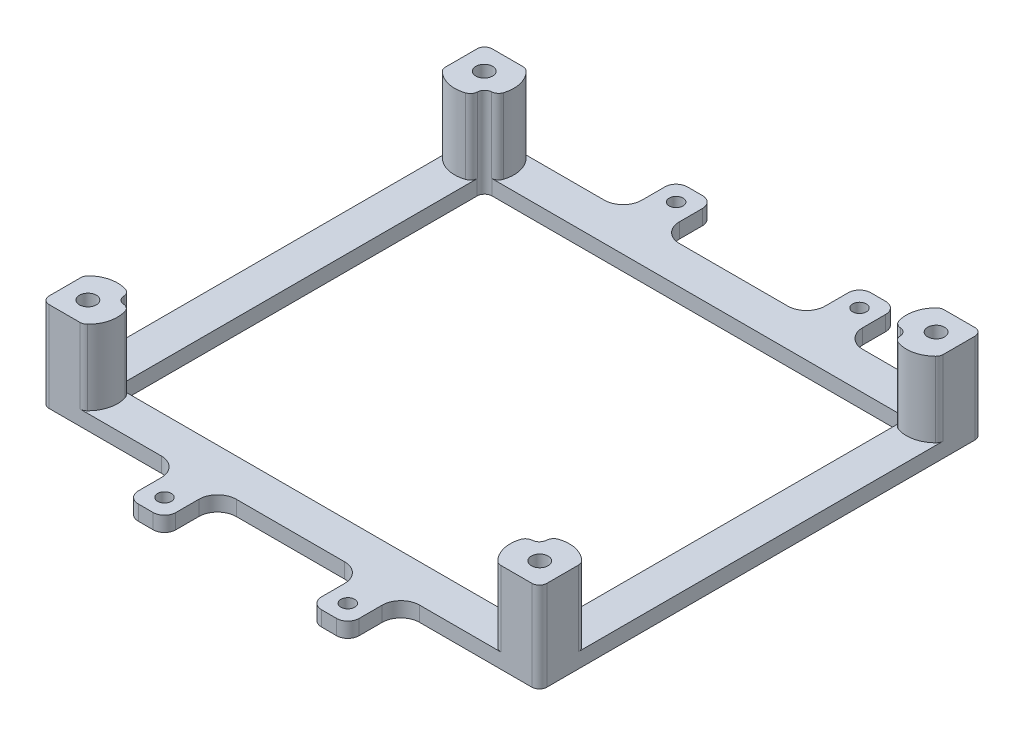
SolidWorks part; units mm, degrees
ref_plane "Front Plane" through (0, 0, 0) normal (0, 0, 1) x (1, 0, 0)
ref_plane "Top Plane" through (0, 0, 0) normal (0, 1, 0) x (1, 0, 0)
ref_plane "Right Plane" through (0, 0, 0) normal (1, 0, 0) x (0, 0, -1)
sketch "Sketch1" plane through (0, 0, 0) normal (0, 1, 0) x (1, 0, 0)
  line L0 (-60.25, 52.85) -> (60.25, -52.85) construction
  line L5 (-60.25, -52.85) -> (60.25, 52.85) construction
  line L6 (-24.4475, -68.2244) -> (24.4475, -68.2244) construction
  line L7 (-66.375, -59.075) -> (66.375, -59.075)
  line L8 (-66.375, -59.075) -> (-66.375, 59.075)
  line L9 (-66.375, 59.075) -> (66.375, 59.075)
  line L10 (66.375, -59.075) -> (66.375, 59.075)
  line L11 (-66.375, -59.075) -> (66.375, 59.075) construction
  line L12 (-66.375, 59.075) -> (66.375, -59.075) construction
  line L13 (-56.375, -49.075) -> (56.375, -49.075)
  line L14 (-56.375, -49.075) -> (-56.375, 49.075)
  line L15 (-56.375, 49.075) -> (56.375, 49.075)
  line L16 (56.375, -49.075) -> (56.375, 49.075)
  line L17 (-56.375, -49.075) -> (56.375, 49.075) construction
  line L18 (-56.375, 49.075) -> (56.375, -49.075) construction
  line L19 (-24.4475, 68.2244) -> (24.4475, 68.2244) construction
  line L20 (-24.4475, 68.2244) -> (-24.4475, -68.2244) construction
  line L21 (0, -55) -> (0, 55) construction
  line L38 (-29.4475, 59.075) -> (-19.4475, 59.075)
  line L39 (-29.4475, 59.075) -> (-29.4475, 73.2244)
  line L40 (-29.4475, 73.2244) -> (-19.4475, 73.2244)
  line L41 (-19.4475, 59.075) -> (-19.4475, 73.2244)
  line L42 (29.4475, 73.2244) -> (19.4475, 73.2244)
  line L43 (19.4475, 59.075) -> (19.4475, 73.2244)
  line L44 (29.4475, 59.075) -> (19.4475, 59.075)
  line L45 (29.4475, 59.075) -> (29.4475, 73.2244)
  line L46 (-55, 0) -> (55, 0) construction
  line L47 (29.4475, -59.075) -> (29.4475, -73.2244)
  line L48 (29.4475, -59.075) -> (19.4475, -59.075)
  line L49 (19.4475, -59.075) -> (19.4475, -73.2244)
  line L50 (29.4475, -73.2244) -> (19.4475, -73.2244)
  line L51 (-29.4475, -73.2244) -> (-19.4475, -73.2244)
  line L52 (-19.4475, -59.075) -> (-19.4475, -73.2244)
  line L53 (-29.4475, -59.075) -> (-19.4475, -59.075)
  line L54 (-29.4475, -59.075) -> (-29.4475, -73.2244)
  circle A0 centre (-60.25, 52.85) radius 2.25
  circle A1 centre (60.25, 52.85) radius 2.25
  circle A2 centre (-60.25, -52.85) radius 2.25
  circle A3 centre (60.25, -52.85) radius 2.25
  circle A4 centre (-24.4475, -68.2244) radius 1.8415
  circle A5 centre (24.4475, -68.2244) radius 1.8415
  circle A6 centre (-24.4475, 68.2244) radius 1.8415
  circle A7 centre (24.4475, 68.2244) radius 1.8415
  arc A8 (-34.4475, 59.075) -> (-29.4475, 64.075) centre (-34.4475, 64.075) ccw
  arc A9 (-14.4475, 59.075) -> (-19.4475, 64.075) centre (-14.4475, 64.075) cw
  arc A10 (34.4475, 59.075) -> (29.4475, 64.075) centre (34.4475, 64.075) cw
  arc A11 (14.4475, 59.075) -> (19.4475, 64.075) centre (14.4475, 64.075) ccw
  arc A12 (34.4475, -59.075) -> (29.4475, -64.075) centre (34.4475, -64.075) ccw
  arc A13 (14.4475, -59.075) -> (19.4475, -64.075) centre (14.4475, -64.075) cw
  arc A14 (-34.4475, -59.075) -> (-29.4475, -64.075) centre (-34.4475, -64.075) cw
  arc A15 (-14.4475, -59.075) -> (-19.4475, -64.075) centre (-14.4475, -64.075) ccw
  point P0 (0, 0)
  point P1 (0, 0)
  point P2 (0, 0)
  point P16 (0, 0)
  point P23 (0, -68.2244)
  point P28 (0, 68.2244)
  point P31 (-24.4475, 0)
  point P76 (0, 59.075)
  point P77 (-66.375, 0)
  dimension "D2" = 4.5
  dimension "D3" = 4.5
  dimension "D4" = 4.5
  dimension "D5" = 4.5
  dimension "D6" = 118.15
  dimension "D11" = 3.683
  dimension "D12" = 3.683
  dimension "D14" = 3.683
  dimension "D15" = 3.683
  dimension "D21" = 10
  dimension "D7" = 132.75
  dimension "D8" = 120.5
  dimension "D9" = 10
  dimension "D10" = 10
  dimension "D13" = 48.895
  dimension "D16" = 48.895
  dimension "D17" = 136.4488
  dimension "D18" = 5
  dimension "D19" = 5
  dimension "D20" = 5
  dimension "D22" = 105.7
extrude "Boss-Extrude3" add sketch "Sketch1" along normal blind 4 contours L9 L41 L40 L39 A6 | L9 L45 L42 L43 A7 | L7 L10 L9 L8 A3 A2 A1 A0 L16 L13 L14 L15 | L7 L54 L51 L52 A4 | L50 L47 L7 L49 A5 | A11 L9 L43 | L9 A10 L45 | A8 L9 L39 | L9 A9 L41 | A15 L7 L52 | L7 A14 L54 | L7 A13 L49 | A12 L7 L47 region at (-64.5979, 0, 0) region at (-30.5643, 0, 60.1918) region at (-24.4475, 0, 65.9808) region at (-30.5643, 0, -60.1918) region at (-18.3307, 0, 60.1918) region at (-24.4475, 0, -65.9808) region at (-18.3307, 0, -60.1918) region at (18.3307, 0, 60.1918) region at (24.4475, 0, 65.9808) region at (18.3307, 0, -60.1918) region at (30.5643, 0, 60.1918) region at (24.4475, 0, -65.9808) region at (30.5643, 0, -60.1918)
fillet "Fillet1" radius 2 8 edges at (56.375, 2, 49.075) (-56.375, 2, 49.075) (56.375, 2, -49.075) (66.375, 2, -59.075) (66.375, 2, 59.075) (-56.375, 2, -49.075) (-66.375, 2, -59.075) (-66.375, 2, 59.075)
fillet "Fillet2" radius 3 8 edges at (-29.4475, 2, -73.2244) (19.4475, 2, -73.2244) (29.4475, 2, -73.2244) (-19.4475, 2, -73.2244) (-29.4475, 2, 73.2244) (-19.4475, 2, 73.2244) (29.4475, 2, 73.2244) (19.4475, 2, 73.2244)
sketch "Sketch3" plane through (0, 4, 0) normal (0, 1, 0) x (1, 0, 0)
  line L0 (-66.375, 47.8504) -> (-66.375, 57.075)
  line L1 (-66.375, -57.075) -> (-66.375, 57.075) construction
  line L2 (-55.3755, 59.075) -> (-64.375, 59.075)
  line L3 (-64.375, 59.075) -> (-34.4475, 59.075) construction
  line L4 (-53.303, 49.075) -> (-54.375, 49.075)
  line L5 (-56.375, 47.075) -> (-56.375, 45.9583)
  line L6 (-56.375, -47.075) -> (-56.375, 47.075) construction
  line L7 (0, -2.2) -> (0, 2.2) construction
  line L8 (56.375, 47.075) -> (56.375, 45.9583)
  line L9 (53.303, 49.075) -> (54.375, 49.075)
  line L10 (55.3755, 59.075) -> (64.375, 59.075)
  line L11 (66.375, 47.8504) -> (66.375, 57.075)
  line L12 (-2.2, 0) -> (2.2, 0) construction
  line L13 (66.375, -47.8504) -> (66.375, -57.075)
  line L14 (55.3755, -59.075) -> (64.375, -59.075)
  line L15 (53.303, -49.075) -> (54.375, -49.075)
  line L16 (56.375, -47.075) -> (56.375, -45.9583)
  line L17 (-56.375, -47.075) -> (-56.375, -45.9583)
  line L18 (-53.303, -49.075) -> (-54.375, -49.075)
  line L19 (-55.3755, -59.075) -> (-64.375, -59.075)
  line L20 (-66.375, -47.8504) -> (-66.375, -57.075)
  circle A0 centre (-60.25, 52.85) radius 2.25
  arc A1 (-66.375, 47.8504) -> (-56.375, 45.9583) centre (-60.25, 52.85) ccw
  arc A2 (-64.375, 59.075) -> (-66.375, 57.075) centre (-64.375, 57.075) ccw construction
  arc A3 (-64.375, 59.075) -> (-66.375, 57.075) centre (-64.375, 57.075) ccw
  arc A4 (-54.375, 49.075) -> (-56.375, 47.075) centre (-54.375, 47.075) ccw
  arc A5 (-53.303, 49.075) -> (-55.3755, 59.075) centre (-60.25, 52.85) ccw
  arc A6 (53.303, 49.075) -> (55.3755, 59.075) centre (60.25, 52.85) cw
  arc A7 (54.375, 49.075) -> (56.375, 47.075) centre (54.375, 47.075) cw
  arc A8 (64.375, 59.075) -> (66.375, 57.075) centre (64.375, 57.075) cw
  arc A9 (66.375, 47.8504) -> (56.375, 45.9583) centre (60.25, 52.85) cw
  circle A10 centre (60.25, 52.85) radius 2.25
  circle A11 centre (60.25, -52.85) radius 2.25
  arc A12 (66.375, -47.8504) -> (56.375, -45.9583) centre (60.25, -52.85) ccw
  arc A13 (64.375, -59.075) -> (66.375, -57.075) centre (64.375, -57.075) ccw
  arc A14 (54.375, -49.075) -> (56.375, -47.075) centre (54.375, -47.075) ccw
  arc A15 (53.303, -49.075) -> (55.3755, -59.075) centre (60.25, -52.85) ccw
  arc A16 (-53.303, -49.075) -> (-55.3755, -59.075) centre (-60.25, -52.85) cw
  arc A17 (-54.375, -49.075) -> (-56.375, -47.075) centre (-54.375, -47.075) cw
  arc A18 (-64.375, -59.075) -> (-66.375, -57.075) centre (-64.375, -57.075) cw
  arc A19 (-66.375, -47.8504) -> (-56.375, -45.9583) centre (-60.25, -52.85) cw
  circle A20 centre (-60.25, -52.85) radius 2.25
extrude "Boss-Extrude5" add sketch "Sketch3" along normal blind 20
fillet "Fillet3" radius 2 16 edges at (-55.3755, 14, 59.075) (-53.303, 14, 49.075) (-56.375, 14, 45.9583) (-66.375, 14, 47.8504) (66.375, 14, 47.8504) (53.303, 14, 49.075) (56.375, 14, 45.9583) (55.3755, 14, 59.075) (-55.3755, 14, -59.075) (-56.375, 14, -45.9583) (-53.303, 14, -49.075) (-66.375, 14, -47.8504) (56.375, 14, -45.9583) (53.303, 14, -49.075) (55.3755, 14, -59.075) (66.375, 14, -47.8504)
